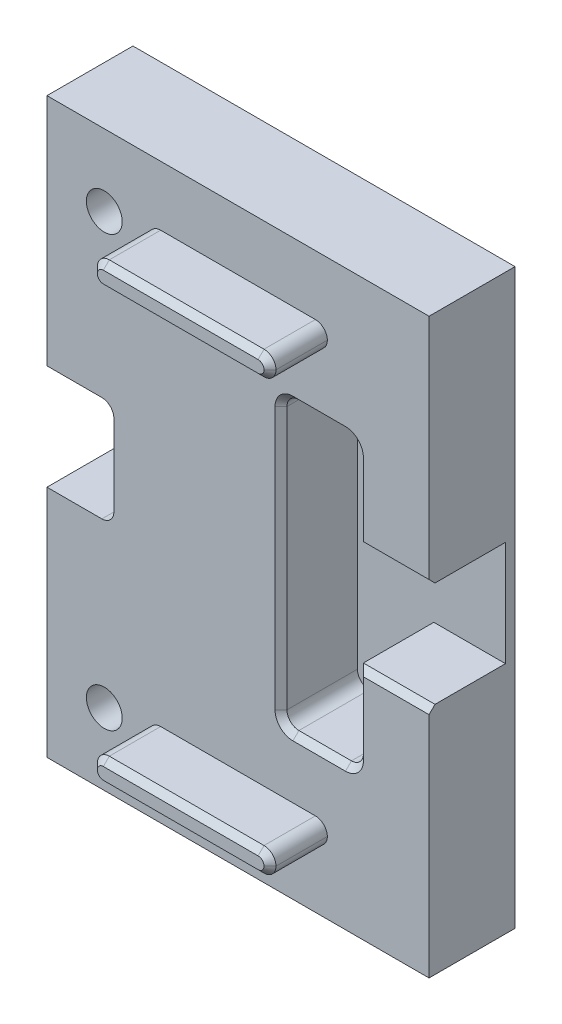
SolidWorks part; units mm, degrees
ref_plane "Front Plane" through (0, 0, 0) normal (1, 0, 0) x (0, 1, 0)
ref_plane "Top Plane" through (0, 0, 0) normal (0, 0, 1) x (0, 1, 0)
ref_plane "Right Plane" through (0, 0, 0) normal (0, 1, 0) x (-1, 0, 0)
sketch "Sketch1" plane through (0, 0, 0) normal (0, 0, 1) x (0, 1, 0)
  line L0 (-38.1, 25.4) -> (38.1, -25.4) construction
  line L1 (-38.1, 25.4) -> (38.1, 25.4)
  line L2 (-38.1, 25.4) -> (-38.1, -25.4)
  line L3 (-38.1, -25.4) -> (38.1, -25.4)
  line L4 (38.1, 25.4) -> (38.1, -25.4)
  line L5 (38.1, 25.4) -> (-38.1, -25.4) construction
  dimension "D1" = 50.8
  dimension "D2" = 76.2
extrude "Boss-Extrude1" add sketch "Sketch1" against normal blind 2.54 contours L2 L3 L4 L1
sketch "Sketch2" plane through (0, 0, 0) normal (0, 0, 1) x (1, 0, 0)
  line L4 (-25.4, 38.1) -> (-25.4, -38.1)
  line L5 (-25.4, -38.1) -> (25.4, -38.1)
  line L6 (25.4, -38.1) -> (25.4, 38.1)
  line L7 (25.4, 38.1) -> (-25.4, 38.1)
  line L8 (-25.4, 38.1) -> (-25.4, -38.1)
  line L9 (-25.4, -38.1) -> (25.4, -38.1)
  line L10 (25.4, -38.1) -> (25.4, 38.1)
  line L11 (25.4, 38.1) -> (-25.4, 38.1)
  dimension "D1" = 0
extrude "Boss-Extrude2" add sketch "Sketch2" along normal blind 8.89
sketch "Sketch3" plane through (0, 0, 8.89) normal (0, 0, 1) x (1, 0, 0)
  line L0 (5.715, 19.05) -> (5.715, -19.05)
  line L2 (5.715, -19.05) -> (15.875, -19.05)
  line L3 (15.875, -19.05) -> (15.875, -6.985)
  line L4 (15.875, -6.985) -> (25.4, -6.985)
  line L5 (25.4, -38.1) -> (25.4, 38.1) construction
  line L6 (25.4, -6.985) -> (25.4, 6.985)
  line L7 (25.4, 6.985) -> (15.875, 6.985)
  line L8 (15.875, 6.985) -> (15.875, 19.05)
  line L9 (15.875, 19.05) -> (5.715, 19.05)
  line L10 (5.715, 0) -> (0, 0) construction
  line L11 (5.715, 0) -> (25.4, 0) construction
  dimension "D1" = 10.16
  dimension "D2" = 38.1
  dimension "D3" = 13.97
  dimension "D4" = 9.525
extrude "Cut-Extrude1" cut sketch "Sketch3" against normal blind 10.16
sketch "Sketch4" plane through (0, 0, 8.89) normal (0, 0, 1) x (1, 0, 0)
  line L0 (-25.4, 6.985) -> (-16.51, 6.985)
  line L1 (-25.4, 38.1) -> (-25.4, -38.1) construction
  line L2 (-16.51, 6.985) -> (-16.51, -6.985)
  line L3 (-16.51, -6.985) -> (-25.4, -6.985)
  line L4 (-25.4, -6.985) -> (-25.4, 6.985)
  line L5 (-16.51, 0) -> (0, 0) construction
  dimension "D1" = 8.89
  dimension "D2" = 13.97
extrude "Cut-Extrude2" cut sketch "Sketch4" against normal through all
sketch "Sketch5" plane through (0, 0, 8.89) normal (0, 0, 1) x (1, 0, 0)
  line L0 (-17.78, 28.575) -> (-17.78, -28.575) construction
  line L1 (-17.78, 0) -> (0, 0) construction
  circle A0 centre (-17.78, 28.575) radius 2.3813
  circle A1 centre (-17.78, -28.575) radius 2.3813
  dimension "D1" = 4.7625
  dimension "D2" = 57.15
  dimension "D3" = 17.78
extrude "Cut-Extrude3" cut sketch "Sketch5" against normal through all contours A1 | A0 region at (-17.78, -28.575, 8.89)
sketch "Sketch9" plane through (0, 0, 8.89) normal (0, 0, 1) x (1, 0, 0)
  line L0 (-11.8745, 26.9875) -> (11.8745, 26.9875)
  line L1 (11.8745, 26.9875) -> (11.8745, 30.1625)
  line L2 (11.8745, 30.1625) -> (-11.8745, 30.1625)
  line L3 (-11.8745, 30.1625) -> (-11.8745, 26.9875)
  line L4 (6.2865, 0) -> (-6.2865, 0) construction
  line L5 (0, 0) -> (0, 30.1625) construction
  line L10 (11.8745, -26.9875) -> (11.8745, -30.1625)
  line L11 (11.8745, -30.1625) -> (-11.8745, -30.1625)
  line L12 (-11.8745, -30.1625) -> (-11.8745, -26.9875)
  line L13 (15.875, 19.05) -> (5.715, 19.05) construction
  line L14 (11.8745, 26.9875) -> (11.8745, 19.05) construction
  line L15 (-15.3987, 28.575) -> (-11.8745, 28.575) construction
  line L16 (-11.8745, -26.9875) -> (11.8745, -26.9875)
  circle A0 centre (-17.78, 28.575) radius 2.3813 construction
  point P2 (0, 0)
  point P26 (0, 0)
  point P28 (0, 0)
  dimension "D1" = 3.175
  dimension "D4" = 23.749
  dimension "D6" = 3.5242
extrude "Boss-Extrude4" add sketch "Sketch9" along normal blind 7.62
fillet "Fillet1" radius 1.5875 14 edges at (5.715, 19.05, 3.81) (15.875, 19.05, 3.81) (5.715, -19.05, 3.81) (15.875, -19.05, 3.81) (-16.51, 6.985, 3.175) (-16.51, -6.985, 3.175) (-11.8745, 30.1625, 12.7) (-11.8745, 26.9875, 12.7) (11.8745, 30.1625, 12.7) (11.8745, 26.9875, 12.7) (-11.8745, -26.9875, 12.7) (-11.8745, -30.1625, 12.7) (11.8745, -26.9875, 12.7) (11.8745, -30.1625, 12.7)
chamfer "Chamfer2" distance 0.7937 angle 45 23 edges at (15.875, 12.2238, 8.89) (15.875, -12.2238, 8.89) (15.41, 18.585, 8.89) (15.41, -18.585, 8.89) (10.795, 19.05, 8.89) (10.795, -19.05, 8.89) (6.18, 18.585, 8.89) (6.18, -18.585, 8.89) (5.715, 0, 8.89) (20.6375, 6.985, 8.89) (20.6375, -6.985, 8.89) (11.4095, 29.6975, 16.51) (11.4095, 27.4525, 16.51) (0, 26.9875, 16.51) (-11.4095, 27.4525, 16.51) (-11.4095, 29.6975, 16.51) (0, 30.1625, 16.51) (11.4095, -27.4525, 16.51) (11.4095, -29.6975, 16.51) (0, -30.1625, 16.51) (-11.4095, -29.6975, 16.51) (-11.4095, -27.4525, 16.51) (0, -26.9875, 16.51)
